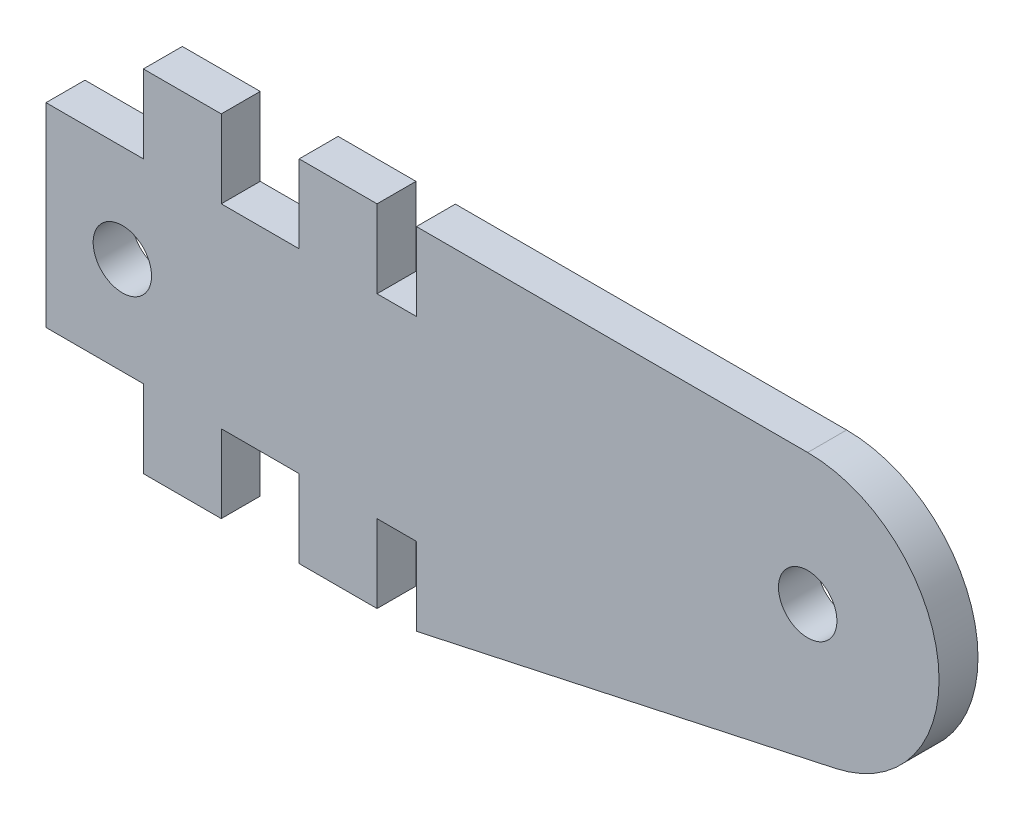
SolidWorks part; units mm, degrees
ref_plane "Front Plane" through (0, 0, 0) normal (0, 0, 1) x (1, 0, 0)
ref_plane "Top Plane" through (0, 0, 0) normal (0, 1, 0) x (1, 0, 0)
ref_plane "Right Plane" through (0, 0, 0) normal (1, 0, 0) x (0, 0, -1)
sketch "Sketch1" plane through (0, 0, 0) normal (0, 0, 1) x (1, 0, 0)
  line L25 (23.6391, 5.9751) -> (24.5074, 10.8992) construction
  line L26 (22.5378, 11.2465) -> (24.5074, 10.8992) construction
  line L28 (21.6695, 6.3224) -> (22.5378, 11.2465) construction
  line L29 (15.6441, 12.462) -> (17.6137, 12.1147) construction
  line L30 (14.7759, 7.538) -> (15.6441, 12.462) construction
  line L31 (16.7455, 7.1907) -> (14.7759, 7.538) construction
  line L39 (16.7455, 7.1907) -> (17.6137, 12.1147) construction
  line L40 (23.6391, 5.9751) -> (21.6695, 6.3224) construction
  line L41 (29.045, 18) -> (29.045, 24.4753) construction
  line L42 (19.0216, 0) -> (40.5426, 4.6622)
  line L43 (19.0216, 4) -> (19.0216, 0)
  line L44 (19.0216, 18) -> (39.1145, 18)
  line L45 (5, 0) -> (9, 0)
  line L46 (5, 4) -> (5, 0)
  line L47 (0, 14) -> (5, 14)
  line L48 (9, 4) -> (13, 4)
  line L49 (13, 4) -> (13, 0)
  line L50 (9, 0) -> (9, 4)
  line L51 (13, 0) -> (17, 0)
  line L52 (17, 0) -> (17, 4)
  line L53 (17, 4) -> (19.0216, 4)
  line L54 (19.0216, 14) -> (19.0216, 18)
  line L55 (0, 4) -> (0, 14)
  line L56 (17, 14) -> (19.0216, 14)
  line L57 (17, 18) -> (17, 14)
  line L58 (13, 18) -> (17, 18)
  line L59 (9, 18) -> (9, 14)
  line L60 (13, 14) -> (13, 18)
  line L61 (9, 14) -> (13, 14)
  line L62 (5, 4) -> (0, 4)
  line L63 (5, 14) -> (5, 18)
  line L64 (5, 18) -> (9, 18)
  circle A3 centre (39.1145, 11.2546) radius 12.12 construction
  circle A5 centre (39.1145, 11.2546) radius 1.5
  circle A6 centre (3.9205, 9) radius 1.5
  arc A7 (39.1145, 18) -> (40.5426, 4.6622) centre (39.1145, 11.2546) cw
  dimension "D1" = 3
  dimension "D2" = 24.24
  dimension "D3" = 6.7453
  dimension "D4" = 3.9205
  dimension "D5" = 5
  dimension "D6" = 9
  dimension "D8" = 40.5426
  dimension "D9" = 4.6622
  dimension "D10" = 9
  dimension "ThumbLinkLengthMCP" = 20.045
extrude "Boss-Extrude1" add sketch "Sketch1" along normal blind 2
equation "\"ThumbLinkLengthMCP@Sketch1\"= \"HB@parametersSketch@prostheticParameters.SLDPRT\" * 0.211"
